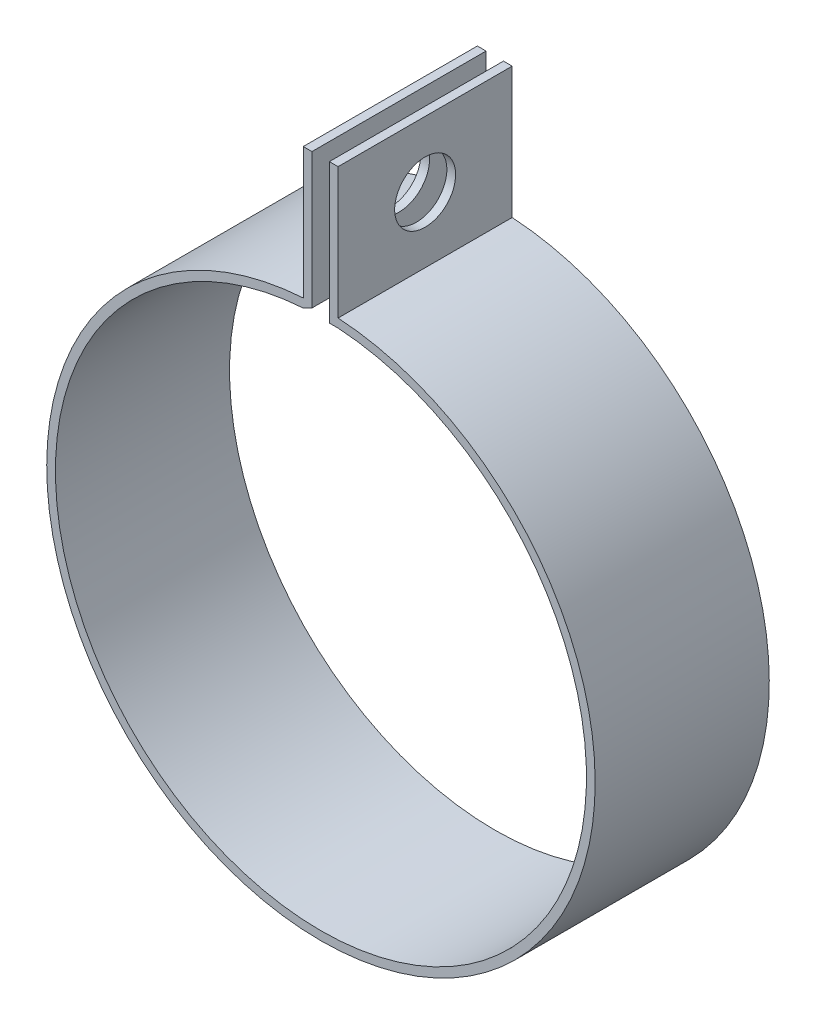
SolidWorks part; units mm, degrees
ref_plane "Alzado" through (0, 0, 0) normal (0, 0, 1) x (1, 0, 0)
ref_plane "Planta" through (0, 0, 0) normal (0, 1, 0) x (1, 0, 0)
ref_plane "Vista lateral" through (0, 0, 0) normal (1, 0, 0) x (0, 0, -1)
sketch "Croquis1" plane through (0, 0, 0) normal (0, 0, 1) x (1, 0, 0)
  line L0 (-1, 15.2172) -> (-0.5161, 15.468)
  line L1 (-1.0161, 23.25) -> (-0.5161, 23.25)
  line L2 (-1.0161, 23.25) -> (-1.0161, 15.7172)
  line L4 (0.9839, 23.25) -> (0.9839, 15.7192)
  line L6 (-0.5161, 23.25) -> (-0.5161, 15.468)
  line L8 (0.4839, 23.25) -> (0.4839, 20.218)
  line L9 (0.4839, 20.218) -> (0.4839, 15.2172)
  line L10 (0.4839, 15.2172) -> (1, 15.2172)
  line L12 (0.4839, 23.25) -> (0.9839, 23.25)
  arc A0 (-1, 15.2172) -> (1, 15.2172) centre (0, 0) ccw
  arc A1 (-1.0161, 15.7172) -> (0.9839, 15.7192) centre (0, 0) ccw
  point P3 (0, 18.25)
  point P4 (0, 15.25)
  dimension "D1" = 30.5
  dimension "D2" = 31.5
  dimension "D3" = 8
  dimension "D4" = 2
  dimension "D5" = 0.5
  dimension "D6" = 0.5
extrude "Saliente-Extruir1" add sketch "Croquis1" along normal blind 10
sketch "Croquis2" plane through (0.9839, 0, 0) normal (1, 0, 0) x (0, 0, -1)
  line L0 (-10, 19.4846) -> (0, 19.4846) construction
  line L1 (-10, 15.7192) -> (-10, 23.25) construction
  line L2 (0, 15.7192) -> (0, 23.25) construction
  line L3 (-5, 19.4846) -> (-5, 23.25) construction
  line L4 (-10, 23.25) -> (0, 23.25) construction
  line L5 (-5, 23.25) -> (-10, 15.7192) construction
  line L6 (-5, 23.25) -> (0, 15.7192) construction
  circle A0 centre (-7.5, 19.4846) radius 0.75 construction
  circle A1 centre (-2.5, 19.4846) radius 0.75 construction
  circle A2 centre (-5, 19.4846) radius 1.75
  dimension "D1" = 1.5
  dimension "D2" = 1.5
  dimension "D3" = 3.5
extrude "Cortar-Extruir1" cut sketch "Croquis2" against normal blind 10
